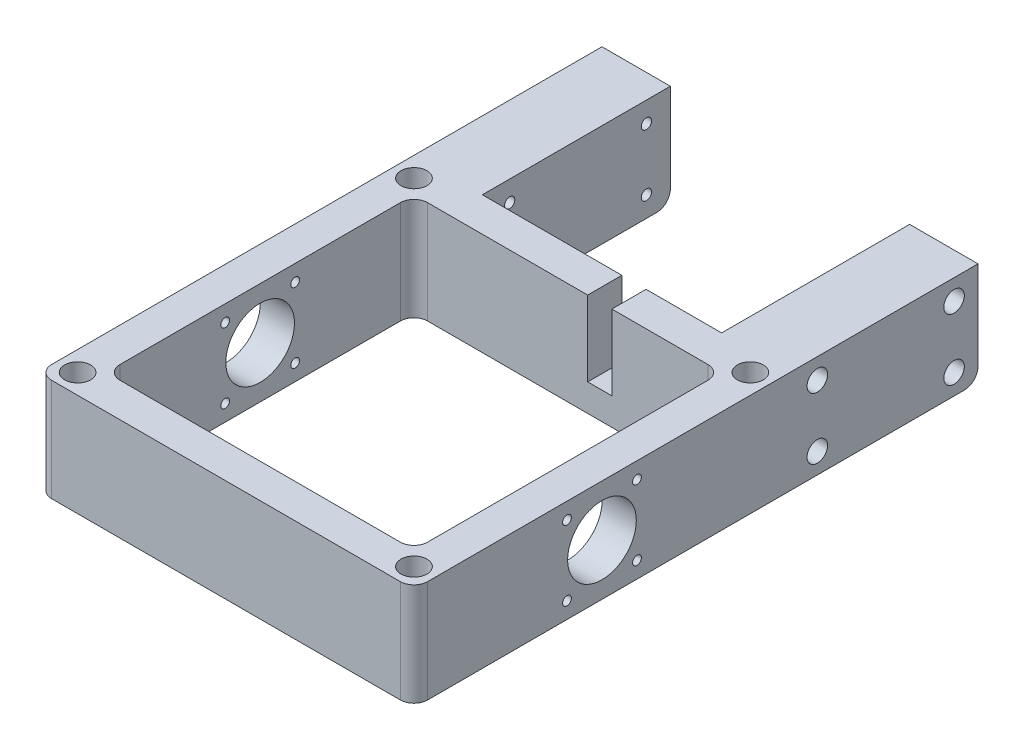
SolidWorks part; units mm, degrees
ref_plane "Front Plane" through (0, 0, 0) normal (0, 0, 1) x (1, 0, 0)
ref_plane "Top Plane" through (0, 0, 0) normal (0, 1, 0) x (1, 0, 0)
ref_plane "Right Plane" through (0, 0, 0) normal (1, 0, 0) x (0, 0, -1)
sketch "Sketch1" plane through (0, 0, 0) normal (0, 1, 0) x (1, 0, 0)
  line L1 (-69.85, 69.85) -> (69.85, 69.85)
  line L2 (-69.85, 69.85) -> (-69.85, -69.85)
  line L3 (-69.85, -69.85) -> (69.85, -69.85)
  line L4 (69.85, 69.85) -> (69.85, -69.85)
  line L5 (-69.85, 69.85) -> (69.85, -69.85) construction
  line L6 (-69.85, -69.85) -> (69.85, 69.85) construction
  line L7 (-69.85, 69.85) -> (-31.75, 69.85)
  line L31 (-69.85, 69.85) -> (-44.45, 69.85)
  line L32 (-69.85, 69.85) -> (-69.85, 139.7)
  line L33 (-69.85, 139.7) -> (-44.45, 139.7)
  line L34 (-44.45, 69.85) -> (-44.45, 139.7)
  line L35 (69.85, 69.85) -> (44.45, 69.85)
  line L36 (69.85, 69.85) -> (69.85, 139.7)
  line L37 (69.85, 139.7) -> (44.45, 139.7)
  line L38 (44.45, 69.85) -> (44.45, 139.7)
  line L39 (-57.15, 57.15) -> (57.15, 57.15)
  line L40 (-57.15, 57.15) -> (-57.15, -57.15)
  line L41 (-57.15, -57.15) -> (57.15, -57.15)
  line L42 (57.15, 57.15) -> (57.15, -57.15)
  line L43 (-57.15, 57.15) -> (57.15, -57.15) construction
  line L44 (-57.15, -57.15) -> (57.15, 57.15) construction
  circle A0 centre (-62.484, -62.484) radius 7.366 construction
  circle A1 centre (-62.484, -62.484) radius 4.826
  circle A2 centre (62.484, -62.484) radius 4.826
  circle A3 centre (62.484, -62.484) radius 7.366 construction
  circle A4 centre (-62.484, 62.484) radius 4.826
  circle A5 centre (-62.484, 62.484) radius 7.366 construction
  circle A6 centre (62.484, 62.484) radius 7.366 construction
  circle A7 centre (62.484, 62.484) radius 4.826
  point P0 (0, 0)
  point P23 (0, 0)
  dimension "D7" = 9.652
  dimension "D8" = 14.732
  dimension "D9" = 9.652
  dimension "D10" = 14.732
  dimension "D11" = 9.652
  dimension "D12" = 14.732
  dimension "D13" = 9.652
  dimension "D15" = 114.3
  dimension "D16" = 114.3
  dimension "D6" = 14.732
  dimension "D1" = 139.7
  dimension "D2" = 139.7
  dimension "D3" = 69.85
  dimension "D4" = 69.85
  dimension "D5" = 88.9
extrude "Boss-Extrude2" add sketch "Sketch1" along normal blind 38.1 contours L1 L34 L33 L32 | L4 L1 L7 L2 L3 A7 A4 A2 A1 L39 L42 L41 L40 | L1 | L35 L38 L37 L36 region at (-57.15, 0, -104.775) region at (-57.15, 0, -67.8743) region at (57.15, 0, -104.775)
sketch "Sketch5" plane through (69.85, 0, 0) normal (1, 0, 0) x (0, 0, -1)
  line L2 (139.7, 38.1) -> (-69.85, 38.1) construction
  line L3 (-13, 6.05) -> (13, 6.05) construction
  line L4 (-13, 6.05) -> (-13, 32.05) construction
  line L5 (-13, 32.05) -> (13, 32.05) construction
  line L6 (13, 6.05) -> (13, 32.05) construction
  line L7 (-13, 6.05) -> (13, 32.05) construction
  line L8 (-13, 32.05) -> (13, 6.05) construction
  circle A0 centre (0, 19.05) radius 12.75
  circle A1 centre (-13, 32.05) radius 1.6319
  circle A2 centre (13, 32.05) radius 1.6319
  circle A3 centre (13, 6.05) radius 1.632
  circle A4 centre (-13, 6.05) radius 1.632
  dimension "D1" = 25.5
  dimension "D2" = 19.05
  dimension ".1160 " = 3.2639
  dimension "D6" = 3.2639
  dimension "D7" = 3.2639
  dimension "D8" = 3.2639
  dimension "D3" = 26
  dimension "D4" = 26
extrude "Cut-Extrude1" cut sketch "Sketch5" against normal up to surface (139.7 mm away) contours A1 | A3 | A4 | A2 | A0 region at (69.85, 32.05, 13) region at (69.85, 32.05, -13) region at (69.85, 6.05, -13) region at (69.85, 6.05, 13) up to face at (-69.85, 19.05, -34.925)
ref_plane "Plane2" through (11.88, 0, 0) normal (-1, 0, 0) x (0, 0, 1)
sketch "Sketch7" plane through (11.88, 0, 0) normal (-1, 0, 0) x (0, 0, 1)
  line L0 (-69.85, 38.1) -> (-69.85, 0) construction
  line L1 (-57.15, 38.1) -> (-57.15, 0) construction
  line L2 (-69.85, 38.1) -> (-69.85, 10.16)
  line L3 (-57.15, 38.1) -> (-57.15, 10.16)
  line L4 (-69.85, 38.1) -> (-57.15, 38.1)
  line L5 (-69.85, 10.16) -> (-57.15, 10.16)
  line L6 (69.85, 0) -> (-139.7, 0) construction
  dimension "D1" = 10.16
extrude "Cut-Extrude2" cut sketch "Sketch7" against normal mid plane 9 contours L4 L3 L5 L2
sketch "Sketch10" plane through (69.85, 0, 0) normal (1, 0, 0) x (0, 0, -1)
  line L0 (139.7, 38.1) -> (139.7, 0) construction
  line L1 (130.81, 7.62) -> (80.01, 7.62) construction
  line L2 (130.81, 7.62) -> (130.81, 30.48) construction
  line L3 (130.81, 30.48) -> (80.01, 30.48) construction
  line L4 (80.01, 7.62) -> (80.01, 30.48) construction
  line L5 (139.7, 0) -> (-69.85, 0) construction
  circle A0 centre (80.01, 30.48) radius 1.905
  circle A1 centre (80.01, 30.48) radius 3.81
  circle A2 centre (130.81, 30.48) radius 1.905
  circle A3 centre (130.81, 7.62) radius 1.905
  circle A4 centre (130.81, 7.62) radius 3.81
  circle A5 centre (130.81, 30.48) radius 3.81
  circle A6 centre (80.01, 7.62) radius 1.905
  circle A7 centre (80.01, 7.62) radius 3.81
  dimension "D5" = 3.81
  dimension "D6" = 3.81
  dimension "D7" = 3.81
  dimension "D8" = 3.81
  dimension "D9" = 7.62
  dimension "D10" = 7.62
  dimension "D11" = 7.62
  dimension "D12" = 7.62
  dimension "D1" = 8.89
  dimension "D2" = 7.62
  dimension "D3" = 22.86
  dimension "D4" = 50.8
extrude "Cut-Extrude3" cut sketch "Sketch10" against normal up to surface (139.7 mm away) contours A0 | A6 | A2 | A3 region at (69.85, 30.48, -80.01) region at (69.85, 7.62, -80.01) up to face at (-69.85, 6.05, -11.3681)
extrude "Cut-Extrude4" cut sketch "Sketch10<3>" against normal blind 15.24
sketch "Sketch10<3>" plane through (69.85, 0, 0) normal (1, 0, 0) x (0, 0, -1) same geometry as "Sketch10"
sketch "Sketch11" plane through (-69.85, 0, 0) normal (-1, 0, 0) x (0, 0, 1)
  line L0 (-80.01, 7.62) -> (-130.81, 7.62) construction
  line L1 (-80.01, 7.62) -> (-80.01, 30.48) construction
  line L2 (-80.01, 30.48) -> (-130.81, 30.48) construction
  line L3 (-130.81, 7.62) -> (-130.81, 30.48) construction
  circle A0 centre (-130.81, 30.48) radius 3.81
  circle A1 centre (-80.01, 7.62) radius 3.81
  circle A2 centre (-80.01, 30.48) radius 3.81
  circle A3 centre (-130.81, 7.62) radius 3.81
  dimension "D1" = 7.62
  dimension "D2" = 7.62
  dimension "D3" = 7.62
  dimension "D4" = 7.62
extrude "Cut-Extrude5" cut sketch "Sketch11" against normal blind 15.24
fillet "Fillet10" radius 5.08 1 edges at (57.15, 19.05, -57.15)
fillet "Fillet11" radius 5.08 1 edges at (-57.15, 19.05, -57.15)
fillet "Fillet12" radius 5.08 1 edges at (-57.15, 19.05, 57.15)
fillet "Fillet13" radius 5.08 1 edges at (57.15, 19.05, 57.15)
fillet "Fillet14" radius 5.08 2 edges at (-57.15, 0, -139.7) (57.15, 0, -139.7)
fillet "Fillet15" radius 5.08 1 edges at (-69.85, 19.05, 69.85) type face fillet first side face at (-69.85, 7.62, -127) second side face at (0, 19.05, 69.85)
fillet "Fillet16" radius 5.08 1 edges at (69.85, 19.05, 69.85) type face fillet first side face at (2.54, 19.05, 69.85) second side face at (69.85, 7.62, -83.82)
equation "\"D1@Plane2\"=(8.3mm/2)+41.12mm"
